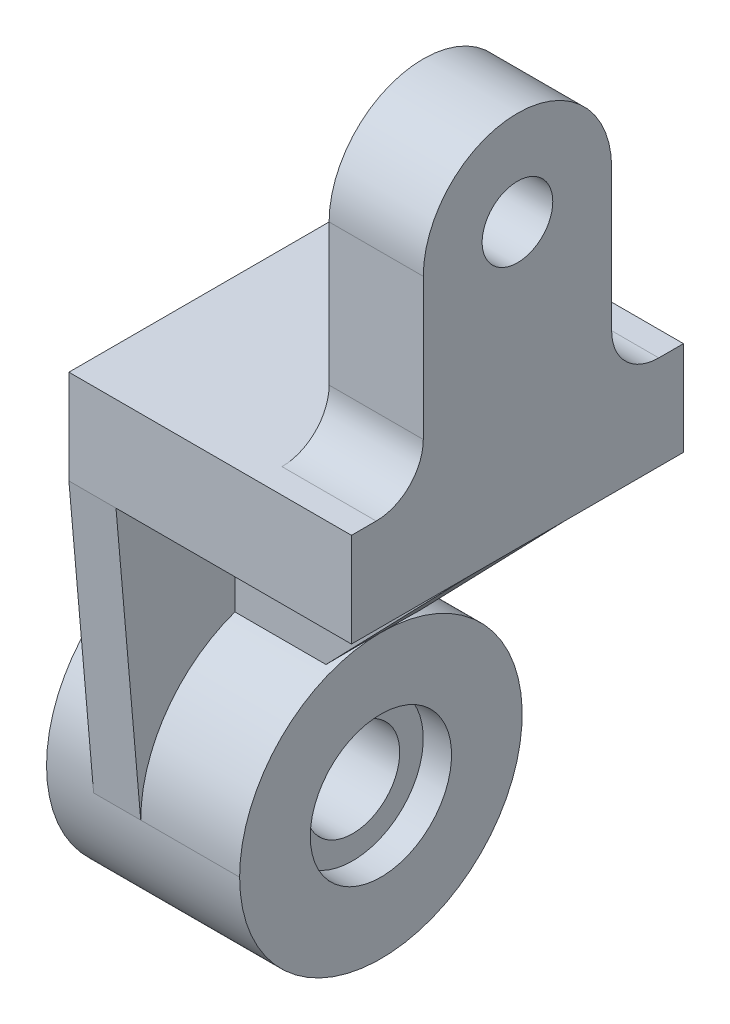
SolidWorks part; units mm, degrees
ref_plane "Front Plane" through (0, 0, 0) normal (0, 0, 1) x (1, 0, 0)
ref_plane "Top Plane" through (0, 0, 0) normal (0, 1, 0) x (1, 0, 0)
ref_plane "Right Plane" through (0, 0, 0) normal (1, 0, 0) x (0, 0, -1)
sketch "Sketch3" plane through (0, 0, 0) normal (0, 1, 0) x (1, 0, 0)
  line L1 (-30, 35.25) -> (30, 35.25)
  line L2 (-30, 35.25) -> (-30, -35.25)
  line L3 (-30, -35.25) -> (30, -35.25)
  line L4 (30, 35.25) -> (30, -35.25)
  line L5 (-30, 35.25) -> (30, -35.25) construction
  line L6 (-30, -35.25) -> (30, 35.25) construction
  point P0 (0, 0)
  dimension "D1" = 70.5
  dimension "D2" = 60
extrude "Boss-Extrude1" add sketch "Sketch3" along normal blind 20
sketch "Sketch4" plane through (30, 0, 0) normal (1, 0, 0) x (0, 0, -1)
  line L0 (0, 60) -> (0, -16.8794) construction
  line L1 (-35.25, 20) -> (35.25, 20) construction
  line L3 (20, 60) -> (20, 30)
  line L4 (-20, 60) -> (-20, 30)
  line L7 (-30, 20) -> (30, 20)
  circle A0 centre (0, 60) radius 7.5
  arc A1 (20, 60) -> (-20, 60) centre (0, 60) ccw
  arc A2 (30, 20) -> (20, 30) centre (30, 30) cw
  arc A3 (-30, 20) -> (-20, 30) centre (-30, 30) ccw
  point P17 (20, 20)
  point P20 (-20, 20)
  dimension "D1" = 15
  dimension "D2" = 40
  dimension "D4" = 10
  dimension "D3" = 40
extrude "Boss-Extrude2" add sketch "Sketch4" against normal blind 20
sketch "Sketch5" plane through (-30, 0, 0) normal (-1, 0, 0) x (0, 0, 1)
  line L0 (0, 100.9285) -> (0, -60) construction
  line L1 (-35.25, 0) -> (35.25, 0) construction
  line L2 (35.25, 0) -> (30, -60)
  line L3 (-35.25, 0) -> (-30, -60)
  line L4 (-35.25, 0) -> (35.25, 0)
  circle A0 centre (0, -60) radius 30
  circle A1 centre (0, -60) radius 15
  circle A2 centre (0, -60) radius 10
  line M5 (-35.25, 0) -> (35.25, 0)
  dimension "D1" = 60
  dimension "D2" = 30
  dimension "D4" = 20
  dimension "D3" = 60
extrude "Boss-Extrude3" add sketch "Sketch5" against normal blind 31 and the other way blind 10 contours A0 A1 region at (-30, -89.1515, 0)
extrude "Boss-Extrude4" add sketch "Sketch5<3>" against normal blind 10 contours L0 L3 A0 M5 | L4 L0 A0 L2 region at (-30, -18.9811, 18.3911) region at (-30, -18.9811, -18.3911)
sketch "Sketch5<3>" plane through (-30, 0, 0) normal (-1, 0, 0) x (0, 0, 1) same geometry as "Sketch5"
extrude "Boss-Extrude6" add sketch "Sketch5<5>" against normal blind 25 and the other way blind 4 contours A1 A2 region at (-30, -60, -14.5757)
sketch "Sketch5<5>" plane through (-30, 0, 0) normal (-1, 0, 0) x (0, 0, 1) same geometry as "Sketch5"
sketch "Sketch6" plane through (0, 0, 0) normal (0, 0, 1) x (1, 0, 0)
  line L0 (30, 0) -> (1, -30)
  line L1 (1, -90) -> (1, -30) construction
  line L2 (-20, 0) -> (-20, -60) construction
  dimension "D1" = 21
rib "Rib1" sketch "Sketch6" sketch "Sketch6" thickness 20 extrusion direction parallel to sketch draft on no parameters "D1"=20
